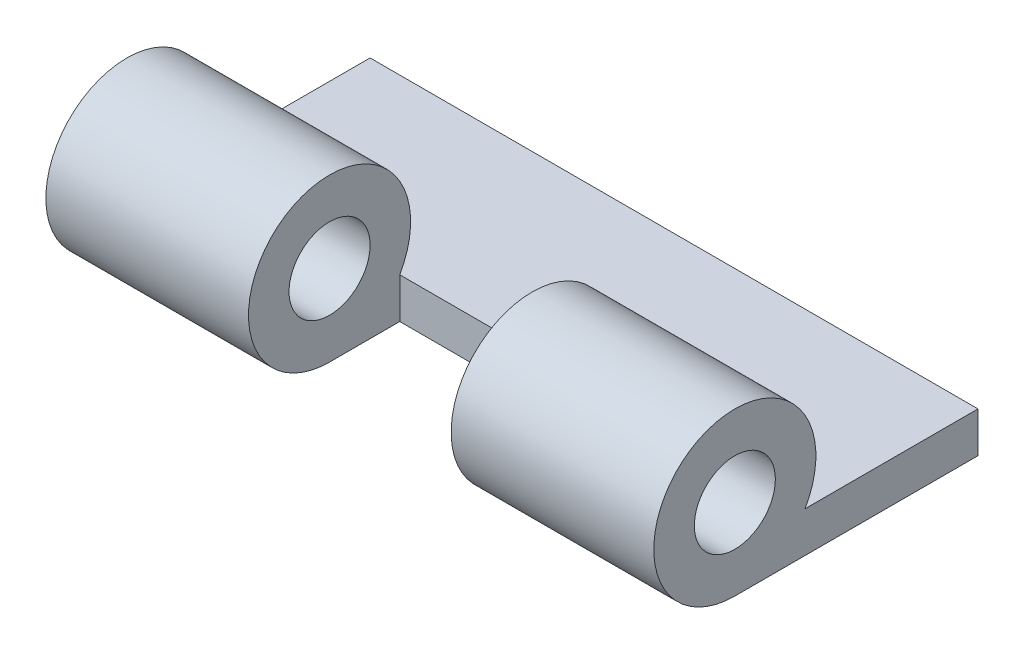
SolidWorks part; units mm, degrees
ref_plane "Ebene vorne" through (0, 0, 0) normal (0, 0, 1) x (1, 0, 0)
ref_plane "Ebene oben" through (0, 0, 0) normal (0, 1, 0) x (1, 0, 0)
ref_plane "Ebene rechts" through (0, 0, 0) normal (1, 0, 0) x (0, 0, -1)
sketch "Skizze1" plane through (0, 0, 0) normal (0, 1, 0) x (1, 0, 0)
  line L1 (0, 0) -> (15, 0)
  line L2 (0, 0) -> (0, 6)
  line L3 (0, 6) -> (15, 6)
  line L4 (15, 0) -> (15, 6)
  dimension "D1" = 15
  dimension "D2" = 6
extrude "Aufsatz-Linear austragen1" add sketch "Skizze1" along normal blind 1
sketch "Skizze2" plane through (15, 0, 0) normal (1, 0, 0) x (0, 0, -1)
  circle A0 centre (0, 2) radius 2
  circle A1 centre (0, 2) radius 1
  dimension "D1" = 2
  dimension "D2" = 1
extrude "Aufsatz-Linear austragen2" add sketch "Skizze2" against normal up to surface (15 mm away) up to face at (0, 0.5, -3)
ref_plane "Tangential Ebene" through (0, 0, -2) normal (0, 0, -1) x (-1, 0, 0)
sketch "Skizze8" plane through (15, 0, 0) normal (1, 0, 0) x (0, 0, -1)
  line L0 (1.7321, 1) -> (1.7321, 0)
  line L1 (1.7321, 0) -> (0, 0)
  line L3 (0, 0) -> (6, 0)
  line L4 (6, 0) -> (6, 1)
  line L5 (6, 1) -> (1.7321, 1)
  line L6 (0, 0) -> (6, 0) construction
  line L7 (6, 0) -> (6, 1) construction
  line L8 (6, 1) -> (1.7321, 1) construction
  arc A1 (1.7321, 1) -> (0, 0) centre (0, 2) ccw
  arc A2 (1.7321, 1) -> (0, 0) centre (0, 2) ccw
  dimension "D1" = 0
extrude "Schnitt-Linear austragen1" cut sketch "Skizze8" against normal blind 5 from offset 5 offset against normal yes
